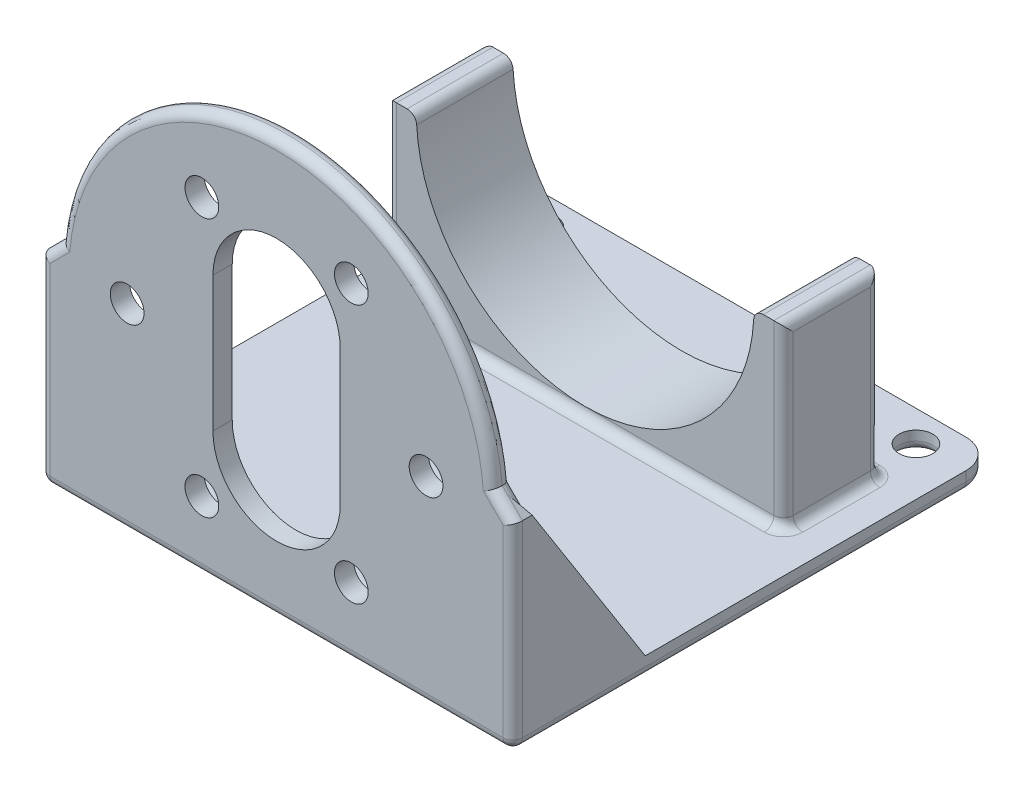
SolidWorks part; units mm, degrees
ref_plane "Alzado" through (0, 0, 0) normal (0, 0, 1) x (1, 0, 0)
ref_plane "Planta" through (0, 0, 0) normal (0, 1, 0) x (1, 0, 0)
ref_plane "Vista lateral" through (0, 0, 0) normal (1, 0, 0) x (0, 0, -1)
sketch "Croquis1" plane through (0, 0, 0) normal (0, 0, 1) x (1, 0, 0)
  line L1 (0, 0) -> (45, 0)
  line L2 (0, 0) -> (0, 18.5)
  line L4 (45, 0) -> (45, 18.5)
  line L14 (15.9, 25.5) -> (15.9, 11.5)
  line L15 (29.1, 25.5) -> (29.1, 11.5)
  arc A0 (45, 18.5) -> (0, 18.5) centre (22.5, 18.5) ccw
  arc A1 (29.1, 25.5) -> (15.9, 25.5) centre (22.5, 25.5) ccw
  arc A2 (15.9, 11.5) -> (29.1, 11.5) centre (22.5, 11.5) ccw
  circle A13 centre (7, 18.5) radius 1.75
  circle A19 centre (22.5, 18.5) radius 18.5 construction
  circle A20 centre (14.75, 31.9234) radius 1.75
  circle A21 centre (30.25, 31.9234) radius 1.75
  circle A22 centre (38, 18.5) radius 1.75
  circle A23 centre (30.25, 5.0766) radius 1.75
  circle A24 centre (14.75, 5.0766) radius 1.75
  point P27 (22.5, 18.5)
  point P28 (21.75, 19.799)
  point P34 (22.5, 18.5)
  dimension "D4" = 45
  dimension "D9" = 13.2
  dimension "D2" = 3.5
  dimension "D7" = 37
  dimension "D3" = 15.5
  dimension "D5" = 18.5
  dimension "D6" = 22.5
  dimension "D8" = 6
  dimension "D11" = 14
  dimension "D12" = 7
extrude "Saliente-Extruir1" add sketch "Croquis1" along normal blind 2
sketch "Croquis6" plane through (0, 0, 2) normal (0, 0, 1) x (1, 0, 0)
  line L0 (0, 18.5) -> (0, 0) construction
  line L1 (-2, 0) -> (47, 0)
  line L2 (-2, 0) -> (-2, -2)
  line L3 (-2, -2) -> (47, -2)
  line L4 (47, 0) -> (47, -2)
  dimension "D1" = 2
  dimension "D2" = 49
  dimension "D3" = 2
extrude "Saliente-Extruir4" add sketch "Croquis6" against normal blind 50
sketch "Croquis7" plane through (0, 0, 0) normal (-1, 0, 0) x (0, 0, 1)
  line L1 (-13, -2) -> (2, -2)
  line L6 (2, -2) -> (2, 18.5)
  line L9 (2, 18.5) -> (0, 18.5)
  line L10 (0, 18.5) -> (-13, -2)
  dimension "D1" = 20.5
  dimension "D2" = 15
extrude "Saliente-Extruir5" add sketch "Croquis7" along normal blind 2
extrude "Saliente-Extruir6" add sketch "Croquis7" against normal blind 2 from offset 45 offset against normal yes
sketch "Croquis9" plane through (0, 0, -48) normal (0, 0, 1) x (1, 0, 0)
  line L0 (5, 18.5) -> (1.9361, 18.5)
  line L1 (1.9361, 18.5) -> (1.9361, -2)
  line L5 (22.5, 18.5) -> (22.5, 11.7632) construction
  line L6 (1.9361, -2) -> (43.0639, -2)
  line L9 (40, 18.5) -> (43.0639, 18.5)
  line L10 (43.0639, 18.5) -> (43.0639, -2)
  arc A1 (5, 18.5) -> (40, 18.5) centre (22.5, 18.5) ccw
  arc A2 (45, 18.5) -> (0, 18.5) centre (22.5, 18.5) ccw construction
  dimension "D1" = 35
extrude "Saliente-Extruir7" add sketch "Croquis9" along normal blind 10 from offset 8
sketch "Croquis8" plane through (0, 0, 0) normal (0, 1, 0) x (1, 0, 0)
  line L0 (0, -2) -> (45, -2) construction
  line L8 (45, 0) -> (45, 11.7317) construction
  circle A0 centre (3, 3.3) radius 1.75
  circle A4 centre (42, 3.3) radius 1.75
  circle A5 centre (3, 44.8) radius 1.75
  circle A6 centre (42, 44.8) radius 1.75
  dimension "D2" = 2
  dimension "D6" = 3.5
  dimension "D9" = 3.5
  dimension "D7" = 3
  dimension "D8" = 3
  dimension "D10" = 5.3
extrude "Cortar-Extruir1" cut sketch "Croquis8" against normal through all
chamfer "Chaflán3" distance 2 angle 45 2 edges at (45, 18.5, 1) (0, 18.5, 1)
fillet "Redondeo4" radius 1 30 edges at (45.951, 19.549, 0) (-0.951, 19.549, 0) (-0.951, 19.549, 2) (45.951, 19.549, 2) (22.5, 41, 0) (22.5, 41, 2) (22.5, -2, 2) (-2, 8.25, 2) (47, 8.25, 2) (0, 0, -5.8659) (45, 0, -5.8659) (47, -2, -23) (22.5, -2, -48) (-2, -2, -23) (43.0639, 0, -35) (1.9361, 0, -35) (3, -2, -1.55) (42, -2, -1.55) (42, -2, -43.05) (3, -2, -43.05) (43.0639, 9.25, -40) (43.0639, 9.25, -30) (1.9361, 9.25, -30) (1.9361, 9.25, -40) (43.0639, 18.5, -35) (1.9361, 18.5, -35) (5, 18.5, -35) (40, 18.5, -35) (22.5, 0, -40) (22.5, 0, -30)
fillet "Redondeo5" radius 3 4 edges at (46.7071, -1.7071, -47.7071) (-1.7071, -1.7071, -47.7071) (-2, -0.5, -48) (47, -0.5, -48)
